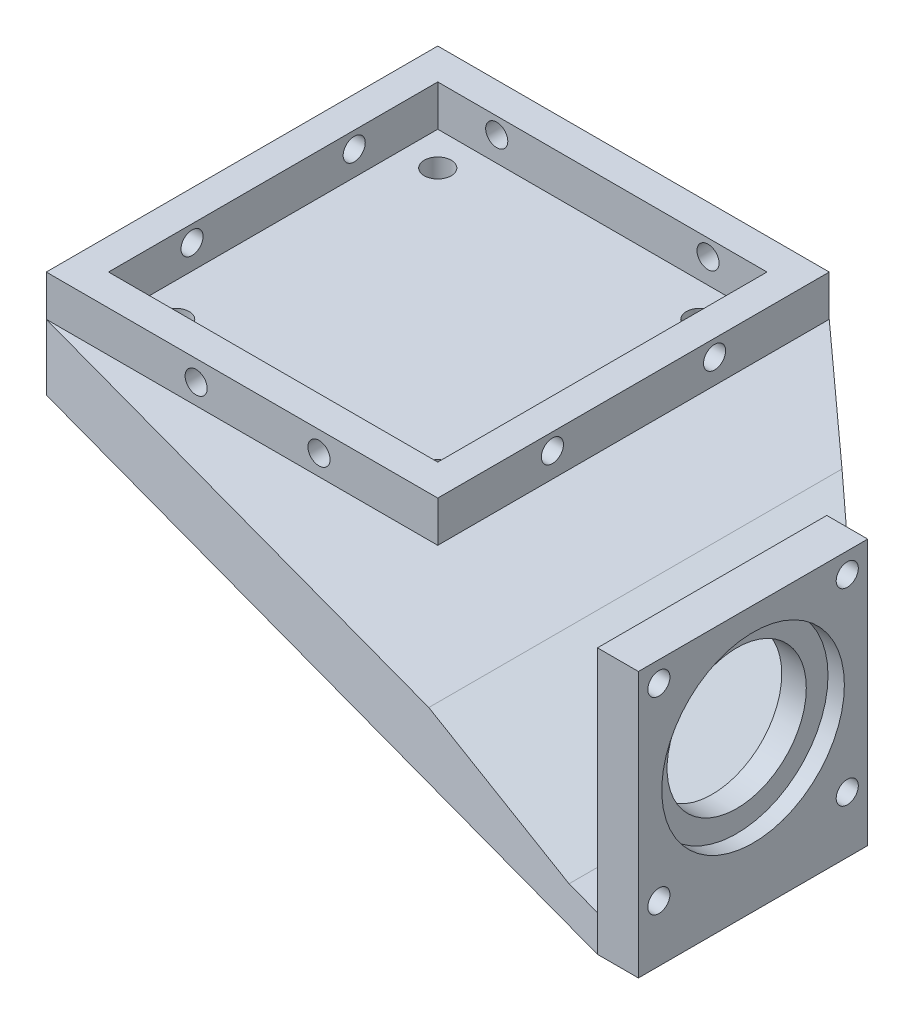
SolidWorks part; units mm, degrees
ref_plane "Front Plane" through (0, 0, 0) normal (0, 0, 1) x (1, 0, 0)
ref_plane "Top Plane" through (0, 0, 0) normal (0, 1, 0) x (1, 0, 0)
ref_plane "Right Plane" through (0, 0, 0) normal (1, 0, 0) x (0, 0, -1)
sketch "Sketch1" plane through (0, 0, 0) normal (0, 1, 0) x (1, 0, 0)
  line L0 (-20.1, 20.1) -> (20.1, -20.1) construction
  line L1 (-20.1, 20.1) -> (20.1, 20.1)
  line L2 (-20.1, 20.1) -> (-20.1, -20.1)
  line L3 (-20.1, -20.1) -> (20.1, -20.1)
  line L4 (20.1, 20.1) -> (20.1, -20.1)
  line L5 (-20.1, -20.1) -> (20.1, 20.1) construction
  line L6 (-23.9, 23.9) -> (-23.9, -23.9)
  line L7 (-23.9, -23.9) -> (23.9, -23.9)
  line L8 (23.9, 23.9) -> (23.9, -23.9)
  line L9 (-23.9, 23.9) -> (23.9, 23.9)
  point P4 (0, 0)
  dimension "D1" = 40.2
  dimension "D2" = 40.2
  dimension "D3" = 3.8
extrude "Boss-Extrude1" add sketch "Sketch1" along normal blind 5
sketch "Sketch6" plane through (0, 0, -23.9) normal (0, 0, -1) x (-1, 0, 0)
  line L0 (-12.9, 3) -> (12.9, 3) construction
  line L1 (23.9, 5) -> (23.9, 0) construction
  line L2 (-23.9, 5) -> (23.9, 5) construction
  circle A0 centre (-12.9, 3) radius 1.35
  circle A1 centre (12.9, 3) radius 1.35
  point P4 (0, 3)
  dimension "D3" = 2.7
  dimension "D4" = 2.7
  dimension "D1" = 11
  dimension "D2" = 2
extrude "Cut-Extrude4" cut sketch "Sketch6" against normal up to next
sketch "Sketch7" plane through (0, 0, 23.9) normal (0, 0, 1) x (1, 0, 0)
  line L0 (23.9, 5) -> (23.9, 0) construction
  line L1 (-23.9, 5) -> (-23.9, 0) construction
  line L2 (-23.9, 5) -> (-23.9, 0) construction
  circle A0 centre (9.4, 2.5) radius 1.35
  circle A1 centre (-5.6, 2.5) radius 1.35
  point P9 (-23.9, 2.5)
  dimension "D1" = 2.7
  dimension "D2" = 2.7
  dimension "D3" = 14.5
  dimension "D4" = 15
extrude "Cut-Extrude5" cut sketch "Sketch7" against normal up to next
sketch "Sketch8" plane through (23.9, 0, 0) normal (1, 0, 0) x (0, 0, -1)
  line L0 (-23.9, 5) -> (-23.9, 0) construction
  line L2 (0, 0) -> (0, 5) construction
  line L3 (-23.9, 5) -> (23.9, 5) construction
  circle A0 centre (-9.9, 3) radius 1.35
  circle A3 centre (9.9, 3) radius 1.35
  dimension "D3" = 2.7
  dimension "D1" = 14
  dimension "D2" = 2
extrude "Cut-Extrude6" cut sketch "Sketch8" against normal through all
sketch "Sketch10" plane through (23.9, 0, 0) normal (1, 0, 0) x (0, 0, -1)
  line L3 (-20.1, 0) -> (-49.5241, 0)
  line L6 (-23.9, 0) -> (23.9, 0) construction
  line L7 (-20.1, 0) -> (-20.1, 5)
  line L8 (-20.1, 5) -> (20.1, 5) construction
  line L9 (-20.1, 5) -> (20.1, 5) construction
  line L10 (-49.5241, 7.0249) -> (-49.5241, 0)
  line L13 (-49.5241, 7.0249) -> (-45.1764, 15.4549)
  line L14 (-45.1764, 15.4549) -> (-44.2876, 14.9965)
  line L15 (-25.4, 10.4128) -> (-24.4, 10.4128)
  line L16 (-20.1, 5) -> (-24.4, 5)
  line L17 (-24.4, 5) -> (-24.4, 10.4128)
  circle A0 centre (-35.4, 10.4128) radius 8.5 construction
  arc A2 (-44.2876, 14.9965) -> (-25.4, 10.4128) centre (-35.4, 10.4128) ccw
  arc A3 (-45.1764, 15.4549) -> (-24.4, 10.4128) centre (-35.4, 10.4128) ccw construction
  dimension "D2" = 17
  dimension "D1" = 20
  dimension "D3" = 22
  dimension "D5" = 5.4128
  dimension "D6" = 15.3
  dimension "D7" = 0.5
sketch "Sketch11" plane through (0, 0, 0) normal (0, 1, 0) x (1, 0, 0)
  line L0 (20.1, 20.1) -> (-20.1, 20.1) construction
  line L1 (-20.1, 20.1) -> (-20.1, -20.1) construction
  line L3 (23.9, -23.9) -> (23.9, 23.9) construction
  line L4 (73.9, -21.4) -> (68.9, -21.4)
  line L5 (73.9, -21.4) -> (73.9, -49.4)
  line L6 (73.9, -49.4) -> (68.9, -49.4)
  line L7 (68.9, -21.4) -> (68.9, -49.4)
  line L8 (68.9, -49.4) -> (-23.9, -23.9)
  line L9 (23.9, 23.9) -> (-23.9, 23.9)
  line L10 (23.9, 23.9) -> (23.9, -23.9)
  line L11 (23.9, -23.9) -> (-23.9, -23.9)
  line L12 (-23.9, 23.9) -> (-23.9, -23.9)
  line L13 (73.9, -21.4) -> (23.9, 23.9)
  circle A0 centre (-16, 16) radius 1.65
  circle A1 centre (16, 16) radius 1.65
  circle A2 centre (16, -16) radius 1.65
  circle A3 centre (-16, -16) radius 1.65
  point P24 (23.9, -35.4)
  point P27 (68.9, -35.4)
  dimension "D3" = 3.3
  dimension "D1" = 4.1
  dimension "D2" = 4.1
  dimension "D6" = 32
  dimension "D7" = 32
  dimension "D8" = 50
  dimension "D9" = 5
  dimension "D10" = 28
  dimension "D4" = 2
  dimension "D5" = 2
extrude "Boss-Extrude8" add sketch "Sketch11" against normal blind 8 contours L4 L13 L10 L11 L8 L7 | L4 L7 L6 L5 | L9 L12 L11 L10 A3 A2 A1 A0 region at (71.4, 0, 35.4) region at (39.57, 0, 19.7754) region at (0, 0, 0)
sketch "Sketch12" plane through (73.9, 0, 0) normal (1, 0, 0) x (0, 0, -1)
  line L0 (-46.9, 21.9128) -> (-23.9, 21.9128) construction
  line L1 (-21.4, -3.5872) -> (-49.4, -3.5872)
  line L2 (-21.4, -3.5872) -> (-21.4, 24.4128)
  line L3 (-21.4, 24.4128) -> (-49.4, 24.4128)
  line L4 (-49.4, -3.5872) -> (-49.4, 24.4128)
  line L5 (-21.4, -3.5872) -> (-49.4, 24.4128) construction
  line L6 (-21.4, 24.4128) -> (-49.4, -3.5872) construction
  line L7 (-46.9, 21.9128) -> (-46.9, -1.0872) construction
  circle A0 centre (-35.4, 10.4128) radius 8.5
  circle A2 centre (-35.4, 10.4128) radius 11.15
  circle A3 centre (-46.9, 21.9128) radius 1.35
  circle A4 centre (-23.9, 21.9128) radius 1.35
  circle A5 centre (-23.9, -1.0872) radius 1.35
  circle A6 centre (-46.9, -1.0872) radius 1.35
  point P0 (-35.4, 10.4128)
  line M2 (-21.4, 0) -> (-49.4, 0)
  line M3 (-49.4, 0) -> (-49.4, -8)
  line M5 (-21.4, -8) -> (-21.4, 0)
  dimension "D1" = 22.3
  dimension "D4" = 2.7
  dimension "D10" = 17
  dimension "D2" = 28
  dimension "D3" = 28
  dimension "D7" = 23
  dimension "D8" = 23
  dimension "D9" = 11.5
  dimension "D5" = 2
  dimension "D6" = 2
sketch "Sketch13" plane through (0, 0, 49.4) normal (0, 0, 1) x (1, 0, 0)
  line L1 (73.9, -3.5872) -> (64.1144, -3.5872)
  line L2 (73.9, -3.5872) -> (73.9, 1.7874)
  line L3 (73.9, 1.7874) -> (28.7381, 1.7874)
  line L4 (64.1144, -3.5872) -> (28.7381, 1.7874)
  line L5 (73.9, -8) -> (73.9, 0) construction
  point P6 (0, 0)
  point P7 (36.1943, 1.6532)
  point P8 (25.6631, 1.5986)
  point P9 (61.1389, -3.308)
  point P11 (73.9, 1.7874)
  point P12 (0, 0)
extrude "Cut-Extrude7" cut sketch "Sketch13" against normal through all
extrude "Boss-Extrude9" add sketch "Sketch12" against normal blind 5 contours A6 A2 A5 L2 L3 L4 A4 A3 M2 | A6 L1 A5 A2 M2 M3 M5 region at (73.9, -1.9444, 35.4) region at (73.9, 0.3715, 22.2498)
extrude "Boss-Extrude10" add sketch "Sketch12<3>" against normal blind 3 from offset 2 contours A2 A0 M2 | A2 M2 region at (73.9, 0.3102, 35.4) region at (73.9, -0.2957, 35.4) offset against normal yes
sketch "Sketch12<3>" plane through (73.9, 0, 0) normal (1, 0, 0) x (0, 0, -1) same geometry as "Sketch12"
